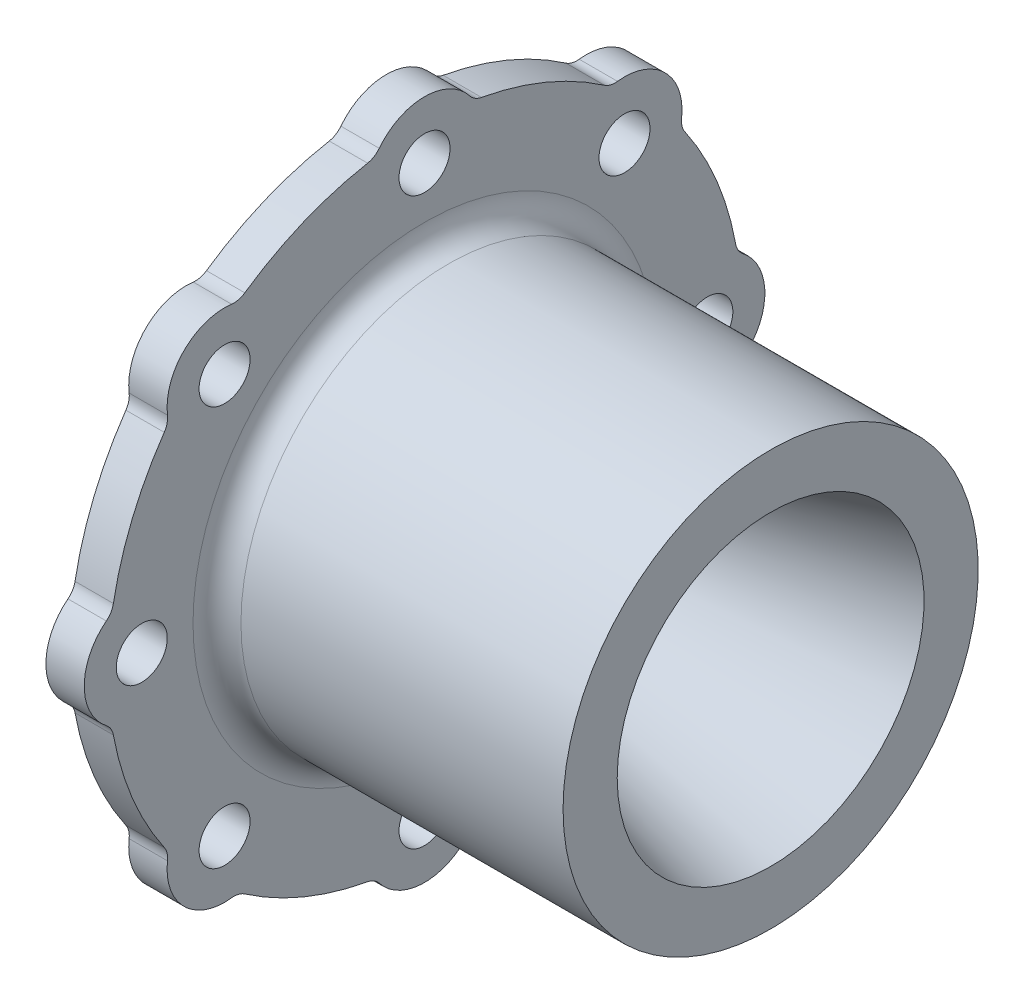
SolidWorks part; units mm, degrees
ref_plane "Front Plane" through (0, 0, 0) normal (0, 0, 1) x (1, 0, 0)
ref_plane "Top Plane" through (0, 0, 0) normal (0, 1, 0) x (1, 0, 0)
ref_plane "Right Plane" through (0, 0, 0) normal (1, 0, 0) x (0, 0, -1)
sketch "Sketch1" plane through (0, 0, 0) normal (0, 0, 1) x (1, 0, 0)
  line L20 (0, 0) -> (32.997, 0) construction
  line L33 (10.9827, 12.3114) -> (21.0157, 12.3114)
  line L34 (10.9827, 12.3114) -> (0, 25.4)
  line L37 (0, 25.4) -> (0, 66.87)
  line L38 (0, 66.87) -> (5.08, 66.87)
  line L39 (5.08, 66.87) -> (5.08, 27.5)
  line L43 (50.9297, 27.5) -> (50.9297, 20.3268)
  line L52 (50.9297, 20.3268) -> (21.0157, 12.3114)
  line L53 (50.9297, 27.5) -> (5.08, 27.5)
  point P1 (2.54, 66.87)
  point P12 (10.9827, 12.3114)
  point P24 (21.0157, 12.3114)
  dimension "D1" = 12.3114
  dimension "D2" = 25.4
  dimension "D5" = 5.08
  dimension "D10" = 15
  dimension "D8" = 20.3268
  dimension "D3" = 27.5
  dimension "D4" = 66.87
  dimension "D6" = 10.033
  dimension "D7" = 50
revolve "Nozzle" add sketch "Sketch1" angle 360 about L20
fillet "Rao outlet radius" radius 4.7029 1 edges at (21.0157, 0, 12.3114)
sketch "Sketch2" plane through (0, 0, 0) normal (-1, 0, 0) x (0, 0, 1)
  point P0 (37.465, 0)
  point P1 (26.4918, -26.4918)
  point P5 (0, -37.465)
  point P6 (-26.4918, -26.4918)
  point P7 (-37.465, 0)
  point P8 (-26.4918, 26.4918)
  point P9 (0, 37.465)
  point P10 (26.4918, 26.4918)
  point P11 (0, 0)
  dimension "D1" = 37.465
hole_wizard "1/4 Clearance Hole1" positions "Sketch2" profile "Sketch3" hole size "1/4" standard "ANSI Inch" end condition through all
sketch "Sketch3" plane through (0, 0, 37.465) normal (0, 1, 0) x (0, 0, 1)
  line L0 (0, 0) -> (0, 50.9297)
  line L1 (0, 50.9297) -> (3.3782, 50.9297)
  line L2 (3.3782, 50.9297) -> (3.3782, 0)
  line L5 (3.3782, 0) -> (0, 0)
  line L11 (0, -6.35) -> (0, 107.95) construction
  dimension "Thru Hole Dia." = 6.7564
  dimension "Thru Hole Depth" = 50.9297
sketch "Sketch5" plane through (0, 0, 0) normal (1, 0, 0) x (0, 0, -1)
  line L0 (0, 0) -> (0, 85.5504) construction
  arc A32 (6.0027, 42.1589) -> (-6.0027, 42.1589) centre (0, 37.465) ccw
  arc A33 (17.8531, 37.9172) -> (7.5462, 41.225) centre (0, 0) ccw
  arc A51 (-7.5462, 41.225) -> (-14.1874, 39.4356) centre (0, 0) ccw
  arc A69 (6.0027, 42.1589) -> (7.5462, 41.225) centre (8.0035, 43.7235) ccw
  arc A70 (-6.0027, 42.1589) -> (-7.5462, 41.225) centre (-8.0035, 43.7235) cw
  arc A72 (34.0554, 25.5663) -> (25.5663, 34.0554) centre (26.4918, 26.4918) ccw
  arc A73 (39.4356, 14.1874) -> (34.4865, 23.8145) centre (0, 0) ccw
  arc A74 (23.8145, 34.4865) -> (17.8531, 37.9172) centre (0, 0) ccw
  arc A75 (34.0554, 25.5663) -> (34.4865, 23.8145) centre (36.5765, 25.2578) ccw
  arc A76 (25.5663, 34.0554) -> (23.8145, 34.4865) centre (25.2578, 36.5765) cw
  arc A77 (42.1589, -6.0027) -> (42.1589, 6.0027) centre (37.465, 0) ccw
  arc A78 (37.9172, -17.8531) -> (41.225, -7.5462) centre (0, 0) ccw
  arc A79 (41.225, 7.5462) -> (39.4356, 14.1874) centre (0, 0) ccw
  arc A80 (42.1589, -6.0027) -> (41.225, -7.5462) centre (43.7235, -8.0035) ccw
  arc A81 (42.1589, 6.0027) -> (41.225, 7.5462) centre (43.7235, 8.0035) cw
  arc A82 (25.5663, -34.0554) -> (34.0554, -25.5663) centre (26.4918, -26.4918) ccw
  arc A83 (14.1874, -39.4356) -> (23.8145, -34.4865) centre (0, 0) ccw
  arc A84 (34.4865, -23.8145) -> (37.9172, -17.8531) centre (0, 0) ccw
  arc A85 (25.5663, -34.0554) -> (23.8145, -34.4865) centre (25.2578, -36.5765) ccw
  arc A86 (34.0554, -25.5663) -> (34.4865, -23.8145) centre (36.5765, -25.2578) cw
  arc A87 (-6.0027, -42.1589) -> (6.0027, -42.1589) centre (0, -37.465) ccw
  arc A88 (-14.2148, -39.4257) -> (-7.5462, -41.225) centre (0, 0) ccw
  arc A89 (7.5462, -41.225) -> (14.1874, -39.4356) centre (0, 0) ccw
  arc A90 (-6.0027, -42.1589) -> (-7.5462, -41.225) centre (-8.0035, -43.7235) ccw
  arc A91 (6.0027, -42.1589) -> (7.5462, -41.225) centre (8.0035, -43.7235) cw
  arc A92 (-34.0554, -25.5663) -> (-25.5663, -34.0554) centre (-26.4918, -26.4918) ccw
  arc A93 (-37.9194, -17.8486) -> (-34.4865, -23.8145) centre (0, 0) ccw
  arc A94 (-23.8145, -34.4865) -> (-14.2148, -39.4257) centre (0, 0) ccw
  arc A95 (-34.0554, -25.5663) -> (-34.4865, -23.8145) centre (-36.5765, -25.2578) ccw
  arc A96 (-25.5663, -34.0554) -> (-23.8145, -34.4865) centre (-25.2578, -36.5765) cw
  arc A97 (-42.1589, 6.0027) -> (-42.1589, -6.0027) centre (-37.465, 0) ccw
  arc A98 (-39.4483, 14.1519) -> (-41.225, 7.5462) centre (0, 0) ccw
  arc A99 (-41.225, -7.5462) -> (-37.9194, -17.8486) centre (0, 0) ccw
  arc A100 (-42.1589, 6.0027) -> (-41.225, 7.5462) centre (-43.7235, 8.0035) ccw
  arc A101 (-42.1589, -6.0027) -> (-41.225, -7.5462) centre (-43.7235, -8.0035) cw
  arc A102 (-25.5663, 34.0554) -> (-34.0554, 25.5663) centre (-26.4918, 26.4918) ccw
  arc A103 (-14.1874, 39.4356) -> (-23.8145, 34.4865) centre (0, 0) ccw
  arc A104 (-34.4865, 23.8145) -> (-39.4483, 14.1519) centre (0, 0) ccw
  arc A105 (-25.5663, 34.0554) -> (-23.8145, 34.4865) centre (-25.2578, 36.5765) ccw
  arc A106 (-34.0554, 25.5663) -> (-34.4865, 23.8145) centre (-36.5765, 25.2578) cw
  point P69 (0, 0)
  point P78 (-6.5261, 41.3988)
  dimension "D3" = 41.91
  dimension "D4" = 2.54
  dimension "D5" = 37.465
  dimension "D6" = 37.465
  dimension "D1" = 8
extrude "Cut-Extrude1" cut sketch "Sketch5" along normal up to surface (5.08 mm away) flip side to cut up to face at (5.08, 0, 40.8432)
fillet "Fillet1" radius 3.175 1 edges at (5.08, 0, 27.5)
fillet "Rao Inlet radius" radius 18.4671 1 edges at (10.9827, 0, 12.3114)
equation "\"radius\"= 1in"
equation "\"Flange\"= 0.55in"
equation "\"Length\"= 2cm"
equation "\"Flange_Thickness\"= 0.2in"
equation "\"offset\"= 0.625cm"
equation "\"D2@Sketch1\"=\"radius\""
equation "\"throat\"= 0.4847in"
equation "\"hole_dia\"= 0.66cm"
equation "\"D1@Sketch1\"=\"throat\""
equation "\"D5@Sketch1\"=\"Flange_Thickness\""
equation "\"Seal_dia\"= 2.5cm"
equation "\"Seal_depth\"= 0.1cm"
equation "\"Seal_width\"= 0.15cm"
equation "\"Nozzle_angle\"= 15"
equation "\"D10@Sketch1\"=\"Nozzle_angle\""
equation "\"nozzle_length\"= 6.34"
equation "\"bolt_head_dia\"=2.3795"
equation "\"bolt_rad\"= \"radius\" + 0.5 * \"Flange\" + 0.2in"
equation "\"scallop_inner_dia\"= 3.3in"
equation "\"exit_rad\"= 1.693cm"
equation "\"D8@Sketch1\"=\"throat\"*(2.726)^0.5"
equation "\"outside_dia\"= 2.75cm"
equation "\"D3@Sketch1\"=\"outside_dia\""
equation "\"D4@Sketch1\"=\"outside_dia\"+\"Flange\"+\"Buffer\""
equation "\"Scallop_OD\"= 0.6in"
equation "\"D3\"= \"Scallop_OD\" / 2"
equation "\"D4\"= \"scallop_inner_dia\" / 2"
equation "\"D2@Sketch5\"=\"Scallop_OD\"/2"
equation "\"D3@Sketch5\"=\"scallop_inner_dia\"/2"
equation "\"D6@Sketch5\"=\"bolt_rad\""
equation "\"D1@Sketch2\"=\"bolt_rad\""
equation "\"Buffer\"= 1in"
equation "\"D1@Rao Inlet radius\"=3*\"throat\""
equation "\"D1@Rao outlet radius\"= 0.382 * \"throat\""
equation "\"D1@Rao Inlet radius\"=1.5*\"throat\""
